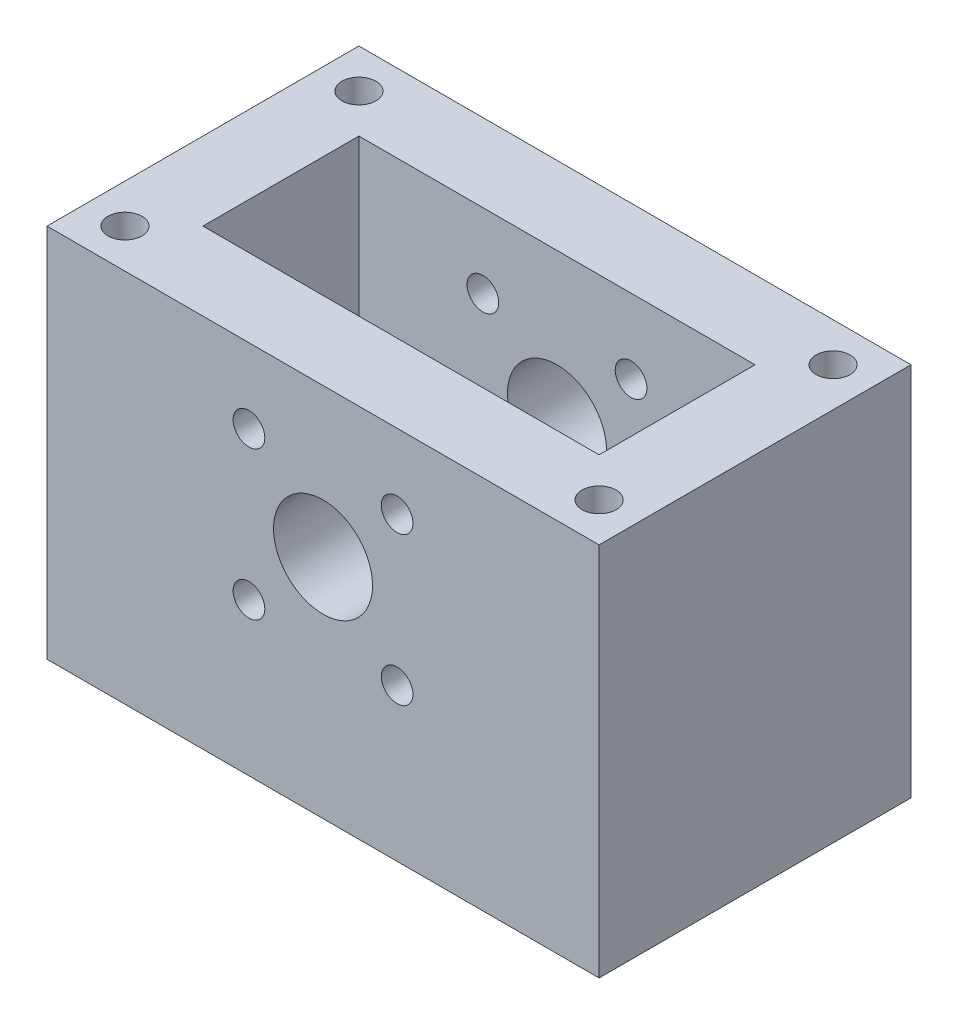
SolidWorks part; units mm, degrees
ref_plane "Front Plane" through (0, 0, 0) normal (0, 0, 1) x (1, 0, 0)
ref_plane "Top Plane" through (0, 0, 0) normal (0, 1, 0) x (1, 0, 0)
ref_plane "Right Plane" through (0, 0, 0) normal (1, 0, 0) x (0, 0, -1)
sketch "Sketch1" plane through (0, 0, 0) normal (0, 0, 1) x (1, 0, 0)
  line L0 (7.9502, -4.7752) -> (17.4498, -4.7752) construction
  line L1 (0, 0) -> (25.4, 0)
  line L2 (0, 0) -> (0, -19.05)
  line L3 (0, -19.05) -> (25.4, -19.05)
  line L4 (25.4, 0) -> (25.4, -19.05)
  line L5 (17.4498, -4.7752) -> (17.4498, -14.2748) construction
  line L6 (0, -19.05) -> (0, -24.05)
  line L7 (0, -24.05) -> (25.4, -24.05)
  line L8 (25.4, -24.05) -> (25.4, -19.05)
  line L9 (25.4, -24.05) -> (30.4, -24.05)
  line L10 (25.4, 0) -> (30.4, 0)
  line L11 (30.4, 0) -> (30.4, -24.05)
  line L12 (0, 0) -> (-5, 0)
  line L13 (-5, 0) -> (-5, -24.05)
  line L14 (-5, -24.05) -> (0, -24.05)
  circle A0 centre (7.9502, -4.7752) radius 1.016
  circle A1 centre (17.4498, -4.7752) radius 1.016
  circle A2 centre (7.9502, -14.2748) radius 1.016
  circle A3 centre (17.4498, -14.2748) radius 1.016
  circle A4 centre (12.7, -9.525) radius 3.175
  point P15 (17.4498, -9.525)
  point P18 (12.7, -4.7752)
  point P20 (12.7, 0)
  point P21 (25.4, -9.525)
  dimension "D3" = 2.032
  dimension "D6" = 6.35
  dimension "D1" = 9.4996
  dimension "D2" = 9.4996
  dimension "D4" = 19.05
  dimension "D5" = 25.4
  dimension "D7" = 5
  dimension "D8" = 5
extrude "Boss-Extrude1" add sketch "Sketch1" along normal blind 5 contours L4 L1 L2 L3 A4 A3 A2 A1 A0 region at (12.7, -0.3175, 0)
extrude "Boss-Extrude2" add sketch "Sketch1<3>" along normal blind 20 contours L7 L8 L3 L6 | L11 L10 L4 L8 L9 | L13 L14 L6 L2 L12 region at (-2.5, -12.025, 0) region at (27.9, -12.025, 0) region at (12.7, -21.55, 0)
sketch "Sketch1<3>" plane through (0, 0, 0) normal (0, 0, 1) x (1, 0, 0) same geometry as "Sketch1"
extrude "Boss-Extrude3" add sketch "Sketch1<4>" against normal blind 5 from surface contours L4 L1 L2 L3 A4 A3 A2 A1 A0 region at (12.7, -0.3175, 0) starting at face at (12.7, -10.775, 20)
sketch "Sketch1<4>" plane through (0, 0, 0) normal (0, 0, 1) x (1, 0, 0) same geometry as "Sketch1"
sketch "Sketch2" plane through (0, 0, 0) normal (0, 1, 0) x (1, 0, 0)
  line L1 (-5, -20) -> (-5, 0) construction
  line L2 (0, -5) -> (-5, -5) construction
  line L3 (25.4, -5) -> (25.4, 0) construction
  line L4 (-5, 0) -> (30.4, 0) construction
  line L5 (25.4, -5) -> (30.4, -5) construction
  line L6 (30.4, -20) -> (30.4, 0) construction
  line L7 (0, -15) -> (0, -20) construction
  line L8 (-5, -20) -> (30.4, -20) construction
  circle A0 centre (-2.5, -2.5) radius 1.0922
  circle A1 centre (27.9, -2.5) radius 1.0922
  circle A2 centre (27.9, -17.5) radius 1.0922
  circle A3 centre (-2.5, -17.5) radius 1.0922
  point P8 (27.9, -5)
  point P9 (0, 0)
  point P29 (0, -17.5)
  dimension "D1" = 2.1844
  dimension "D2" = 5
  dimension "D3" = 2.5
  dimension "D4" = 2.5
extrude "Cut-Extrude1" cut sketch "Sketch2" against normal blind 10
equation "\"D2@Sketch1\"=\"D1@Sketch1\""
equation "\"D8@Sketch1\"=\"D7@Sketch1\""
equation "\"D3@Sketch2\"=\"D2@Sketch2\"/2"
equation "\"D4@Sketch2\"=\"D3@Sketch2\""
